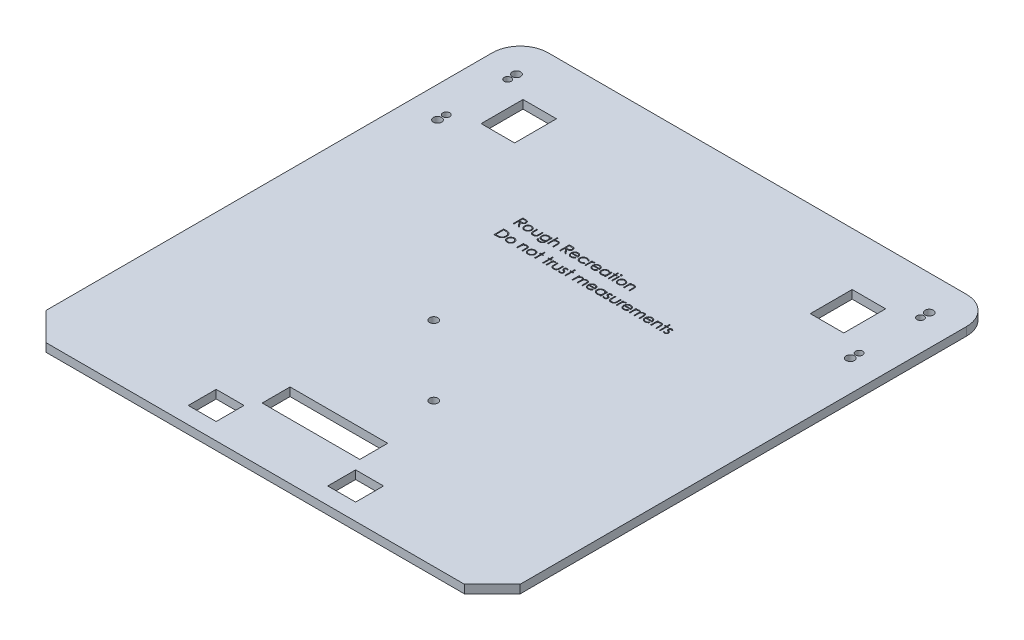
SolidWorks part; units mm, degrees
ref_plane "Front Plane" through (0, 0, 0) normal (0, 0, 1) x (1, 0, 0)
ref_plane "Top Plane" through (0, 0, 0) normal (0, 1, 0) x (1, 0, 0)
ref_plane "Right Plane" through (0, 0, 0) normal (1, 0, 0) x (0, 0, -1)
sketch "Sketch1" plane through (0, 0, 0) normal (0, 1, 0) x (1, 0, 0)
  line L1 (-85, 90) -> (85, 90)
  line L2 (-85, 90) -> (-85, -90)
  line L3 (-85, -90) -> (85, -90)
  line L4 (85, 90) -> (85, -90)
  line L5 (-85, 90) -> (85, -90) construction
  line L6 (-85, -90) -> (85, 90) construction
  point P0 (0, 0)
  dimension "D1" = 180
  dimension "D2" = 170
extrude "Boss-Extrude1" add sketch "Sketch1" along normal blind 3
fillet "FrontRound" radius 10 2 edges at (85, 1.5, -90) (-85, 1.5, -90)
chamfer "BackChamfer" distance 10 angle 45 2 edges at (85, 1.5, 90) (-85, 1.5, 90)
sketch "Sketch2" plane through (0, 0, 0) normal (0, 1, 0) x (1, 0, 0)
  line L0 (-59, 63.5) -> (-80.3094, 63.5) construction
  line L1 (-65, 71) -> (-53, 71)
  line L2 (-65, 71) -> (-65, 56)
  line L3 (-65, 56) -> (-53, 56)
  line L4 (-53, 71) -> (-53, 56)
  line L5 (-65, 71) -> (-53, 56) construction
  line L6 (-65, 56) -> (-53, 71) construction
  line L7 (75, 90) -> (-75, 90) construction
  line L8 (-85, 80) -> (-85, -80) construction
  line L9 (-74, 74.5) -> (-74, 86.3974) construction
  circle A0 centre (-74, 77.65) radius 1.5
  circle A1 centre (-74, 74.5) radius 1.25
  circle A2 centre (-74, 52.5) radius 1.25
  circle A3 centre (-74, 49.35) radius 1.5
  point P0 (-59, 63.5)
  dimension "D1" = 3
  dimension "D2" = 2.5
  dimension "D3" = 12
  dimension "D4" = 15
  dimension "D5" = 9
  dimension "D6" = 22
  dimension "D7" = 28.3
  dimension "D8" = 19
  dimension "D9" = 20
extrude "MotorMount" cut sketch "Sketch2" along normal through all
mirror "MotorMount2" about plane through (0, 0, 0) normal (1, 0, 0) of "MotorMount"
sketch "Sketch3" plane through (0, 0, 0) normal (0, 1, 0) x (1, 0, 0)
  line L0 (0, 0) -> (0, -64.1859) construction
  line L1 (-32.0087, -26) -> (26.7862, -26) construction
  line L2 (-75, -90) -> (75, -90) construction
  line L3 (-23.2545, -2.7455) -> (24.8813, -50.8813) construction
  line L4 (20.5695, -5.4305) -> (-28.1207, -54.1207) construction
  circle A0 centre (-12.5, -13.5) radius 1.5
  circle A1 centre (12.5, -38.5) radius 1.5
  point P9 (0, -26)
  point P10 (0, -26)
  dimension "D1" = 3
  dimension "D3" = 25
  dimension "D4" = 64
  dimension "D5" = 25
extrude "CasterHoles" cut sketch "Sketch3" along normal through all
sketch "Sketch4" plane through (0, 0, 0) normal (0, 1, 0) x (1, 0, 0)
  line L0 (0, 0) -> (0, -89.2874) construction
  line L1 (30, -84) -> (20, -74) construction
  line L2 (-17.5, -60) -> (17.5, -60)
  line L3 (-17.5, -60) -> (-17.5, -70)
  line L4 (-17.5, -70) -> (17.5, -70)
  line L5 (17.5, -60) -> (17.5, -70)
  line L6 (-17.5, -60) -> (17.5, -70) construction
  line L7 (-17.5, -70) -> (17.5, -60) construction
  line L8 (-30, -74) -> (-20, -74)
  line L9 (-30, -74) -> (-30, -84)
  line L10 (-30, -84) -> (-20, -84)
  line L11 (-20, -74) -> (-20, -84)
  line L12 (-30, -74) -> (-20, -84) construction
  line L13 (-30, -84) -> (-20, -74) construction
  line L14 (30, -74) -> (20, -84) construction
  line L15 (20, -74) -> (20, -84)
  line L16 (30, -84) -> (20, -84)
  line L17 (30, -74) -> (30, -84)
  line L18 (30, -74) -> (20, -74)
  line L19 (-75, -90) -> (75, -90) construction
  text T0 "Rough Recreation\r\nDo not trust measurements"
  point P3 (0, -65)
  point P8 (-25, -79)
  point P17 (25, -79)
  point P20 (-20, -79)
  dimension "D1" = 10
  dimension "D2" = 10
  dimension "D3" = 35
  dimension "D4" = 10
  dimension "D5" = 6
  dimension "D6" = 40
  dimension "D7" = 4
extrude "SensorMount" cut sketch "Sketch4" along normal through all
